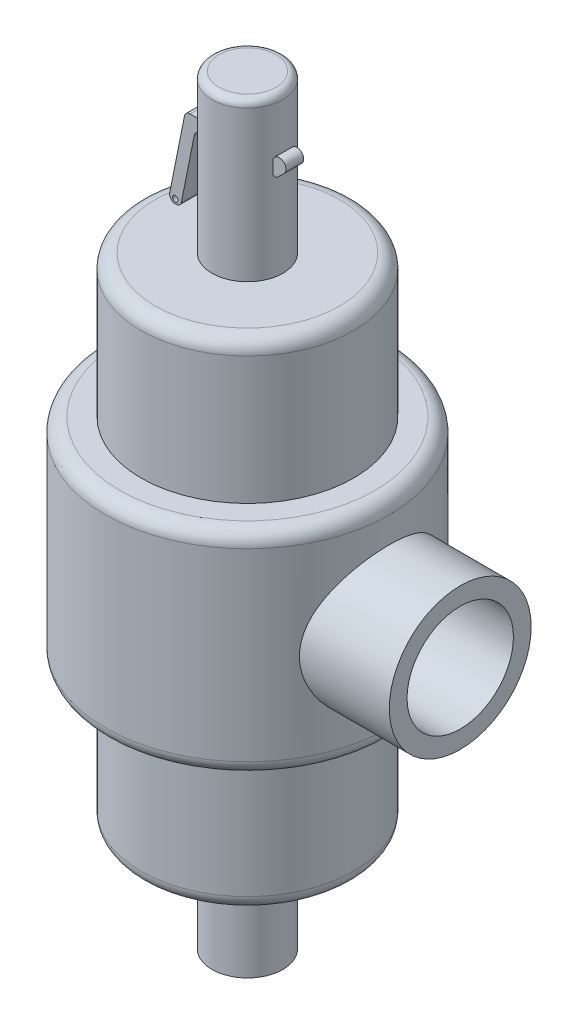
SolidWorks part; units mm, degrees
ref_plane "Front Plane" through (0, 0, 0) normal (0, 0, 1) x (1, 0, 0)
ref_plane "Top Plane" through (0, 0, 0) normal (0, 1, 0) x (1, 0, 0)
ref_plane "Right Plane" through (0, 0, 0) normal (1, 0, 0) x (0, 0, -1)
sketch "Sketch1" plane through (0, 0, 0) normal (0, 1, 0) x (1, 0, 0)
  circle A0 centre (0, 0) radius 6.35
extrude "Boss-Extrude1" add sketch "Sketch1" along normal blind 19.05
sketch "Sketch2" plane through (0, 19.05, 0) normal (0, 1, 0) x (1, 0, 0)
  circle A0 centre (0, 0) radius 19.05
  dimension "D1" = 38.1
extrude "Boss-Extrude2" add sketch "Sketch2" along normal blind 25.4
sketch "Sketch3" plane through (0, 44.45, 0) normal (0, 1, 0) x (1, 0, 0)
  circle A0 centre (0, 0) radius 25.4
  dimension "D1" = 50.8
extrude "Boss-Extrude3" add sketch "Sketch3" along normal blind 38.1
sketch "Sketch4" plane through (0, 82.55, 0) normal (0, 1, 0) x (1, 0, 0)
  circle A0 centre (0, 0) radius 19.05
  dimension "D1" = 38.1
extrude "Boss-Extrude4" add sketch "Sketch4" along normal blind 25.4
sketch "Sketch6" plane through (0, 107.95, 0) normal (0, 1, 0) x (1, 0, 0)
  circle A0 centre (0, 0) radius 6.35
  dimension "D1" = 12.7
extrude "Boss-Extrude5" add sketch "Sketch6" along normal blind 28.194
ref_plane "Plane1" through (0, 0, 19.05) normal (0, 0, 1) x (1, 0, 0)
sketch "Sketch8" plane through (0, 0, 0) normal (1, 0, 0) x (0, 0, -1)
  line L0 (-6.35, 0) -> (6.35, 0) construction
  circle A0 centre (0, 62.6872) radius 12.7
  circle A1 centre (0, 62.6872) radius 9.525
  dimension "D1" = 62.6872
extrude "Boss-Extrude7" add sketch "Sketch8" along normal blind 38.1
sketch "Sketch9" plane through (0, 0, 0) normal (0, 0, 1) x (1, 0, 0)
  line L0 (8.1145, 125.074) -> (6.8061, 123.815)
  line L1 (6.8061, 123.815) -> (-6.9376, 123.815)
  line L2 (-7.934, 122.9975) -> (-10.2308, 111.4732)
  line L3 (-11.2272, 110.6558) -> (-11.3326, 110.6558)
  line L4 (-12.329, 111.8704) -> (-9.6885, 125.1199)
  line L5 (-8.6921, 125.9373) -> (6.0856, 125.9373)
  arc A0 (8.1145, 125.074) -> (6.0856, 125.9373) centre (7.2838, 125.9373) ccw
  arc A1 (-10.2308, 111.4732) -> (-11.2272, 110.6558) centre (-11.2272, 111.6718) cw
  arc A2 (-6.9376, 123.815) -> (-7.934, 122.9975) centre (-6.9376, 122.799) ccw
  arc A3 (-9.6885, 125.1199) -> (-8.6921, 125.9373) centre (-8.6921, 124.9213) cw
  arc A4 (-11.3326, 110.6558) -> (-12.329, 111.8704) centre (-11.3326, 111.6718) cw
  circle A5 centre (7.2838, 125.9373) radius 0.5592
  dimension "D1" = 1.016
  dimension "D2" = 1.016
extrude "Boss-Extrude8" add sketch "Sketch9" along normal blind 1.5875 and the other way blind 1.5875 contours L5 A0 L0 L1 A2 L2 A1 L3 A4 L4 A3
fillet "Fillet1" radius 2.54 4 edges at (0, 19.05, 19.05) (0, 44.45, 25.4) (0, 82.55, 25.4) (0, 107.95, 19.05)
fillet "Fillet3" radius 1.27 1 edges at (0, 136.144, 6.35)
sketch "Sketch10" plane through (0, 0, 1.5875) normal (0, 0, 1) x (1, 0, 0)
  circle A0 centre (-11.3151, 111.469) radius 0.4928
  arc A2 (-11.2272, 110.6558) -> (-10.2308, 111.4732) centre (-11.2272, 111.6718) ccw construction
  dimension "D1" = 0.2211
extrude "Cut-Extrude1" cut sketch "Sketch10" against normal up to next
